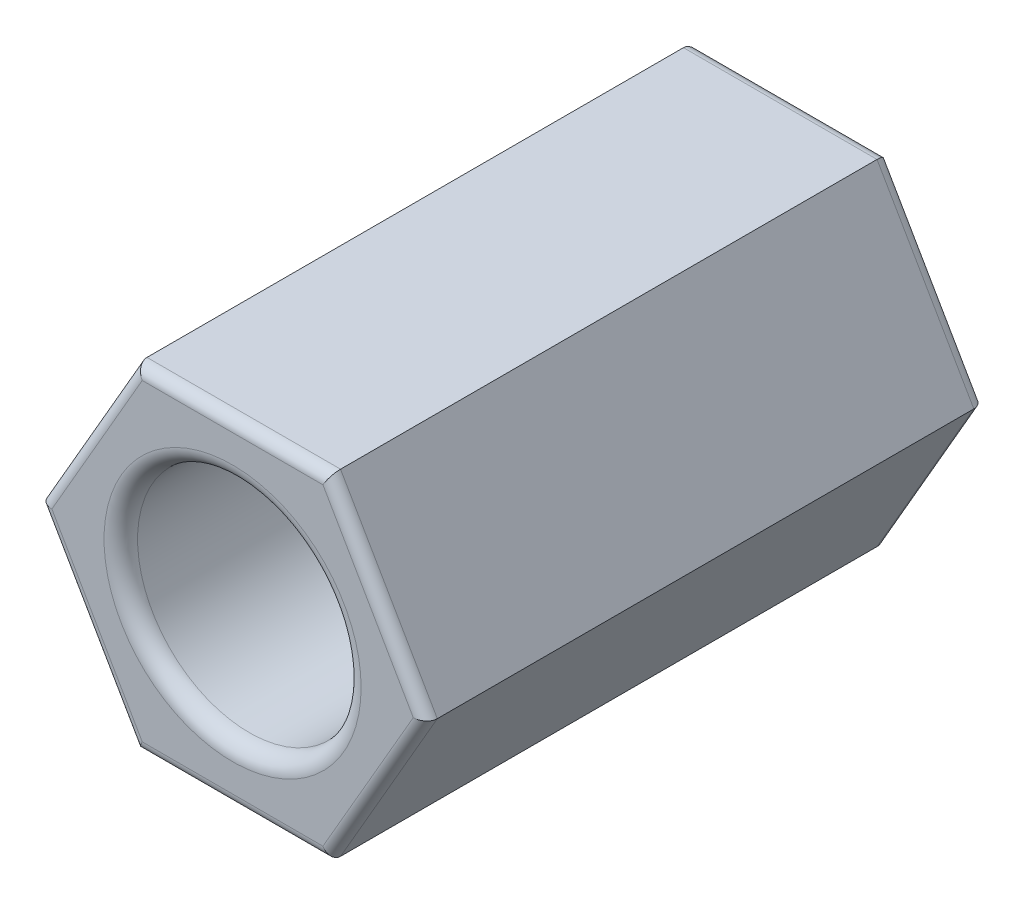
SolidWorks part; units mm, degrees
ref_plane "Front Plane" through (0, 0, 0) normal (0, 0, 1) x (1, 0, 0)
ref_plane "Top Plane" through (0, 0, 0) normal (0, 1, 0) x (1, 0, 0)
ref_plane "Right Plane" through (0, 0, 0) normal (1, 0, 0) x (0, 0, -1)
ref_axis "Axis1" through (0, 0, -1.7581) along (0, 0, 1)
sketch "Sketch1" plane through (0, 0, 0) normal (0, 0, 1) x (1, 0, 0)
  line L1 (3.4641, 0) -> (1.7321, 3)
  line L2 (1.7321, 3) -> (-1.7321, 3)
  line L3 (-1.7321, 3) -> (-3.4641, 0)
  line L4 (-3.4641, 0) -> (-1.7321, -3)
  line L5 (-1.7321, -3) -> (1.7321, -3)
  line L6 (1.7321, -3) -> (3.4641, 0)
  circle A0 centre (0, 0) radius 3 construction
  circle A1 centre (0, 0) radius 2
  dimension "D2" = 4
  dimension "D1" = 6
extrude "Boss-Extrude1" add sketch "Sketch1" along normal blind 10
fillet "Fillet1" radius 0.3 2 edges at (2, 0, 0) (2, 0, 10)
fillet "Fillet2" radius 0.2 12 edges at (-2.5981, 1.5, 10) (-2.5981, -1.5, 10) (0, -3, 10) (2.5981, -1.5, 10) (2.5981, 1.5, 10) (0, 3, 10) (2.5981, -1.5, 0) (0, -3, 0) (-2.5981, -1.5, 0) (-2.5981, 1.5, 0) (0, 3, 0) (2.5981, 1.5, 0)
